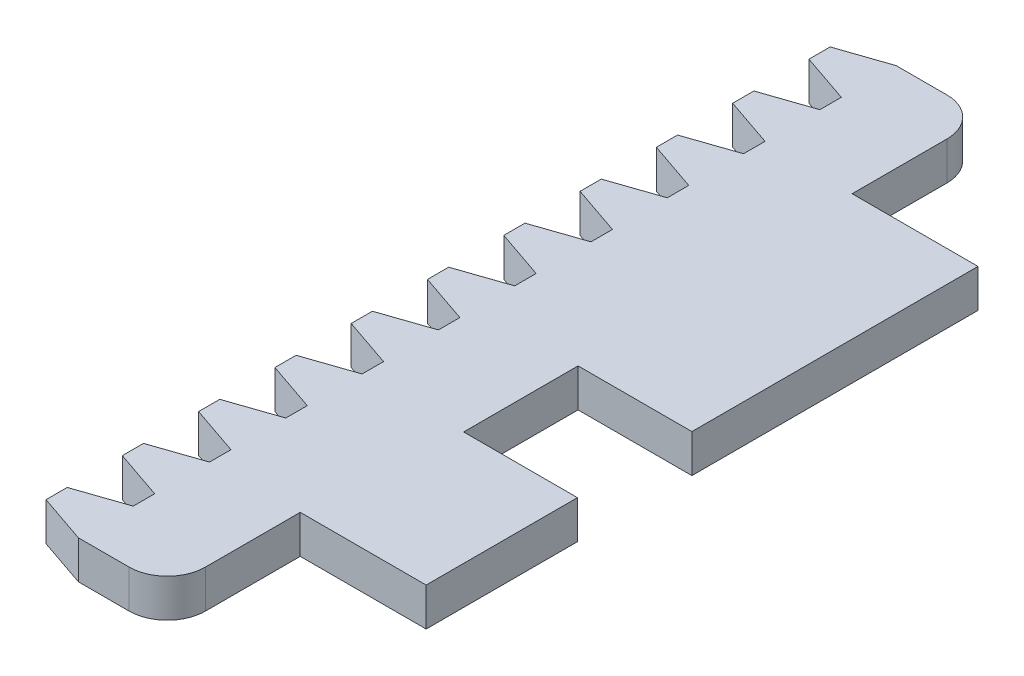
SolidWorks part; units mm, degrees
ref_plane "Front Plane" through (0, 0, 0) normal (0, 0, 1) x (1, 0, 0)
ref_plane "Top Plane" through (0, 0, 0) normal (0, 1, 0) x (1, 0, 0)
ref_plane "Right Plane" through (0, 0, 0) normal (1, 0, 0) x (0, 0, -1)
sketch "Sketch1" plane through (0, 0, 0) normal (0, 1, 0) x (1, 0, 0)
  line L4 (37.95, 21.7) -> (28.05, 21.7) construction
  line L5 (28.05, 29.157) -> (28.05, 21.7) construction
  line L6 (21.0585, 32.157) -> (25.05, 32.157) construction
  line L7 (21.0585, 32.157) -> (17.1887, 30.8335) construction
  line L8 (17.1887, 30.8335) -> (17.1887, 29.1665) construction
  line L13 (17.1887, 29.1665) -> (21.0585, 27.843) construction
  line L14 (21.0585, 26.157) -> (21.0585, 27.843) construction
  line L15 (21.0585, 26.157) -> (17.1887, 24.8335) construction
  line L16 (17.1887, 24.8335) -> (17.1887, 23.1665) construction
  line L17 (17.1887, 23.1665) -> (21.0585, 21.843) construction
  line L18 (21.0585, 20.157) -> (21.0585, 21.843) construction
  line L19 (21.0585, 20.157) -> (17.1887, 18.8335) construction
  line L20 (17.1887, 18.8335) -> (17.1887, 17.1665) construction
  line L21 (17.1887, 17.1665) -> (21.0585, 15.843) construction
  line L22 (21.0585, 14.157) -> (21.0585, 15.843) construction
  line L23 (21.0585, 14.157) -> (17.1887, 12.8335) construction
  line L24 (17.1887, 12.8335) -> (17.1887, 11.1665) construction
  line L25 (17.1887, 11.1665) -> (21.0585, 9.843) construction
  line L26 (21.0585, 8.157) -> (21.0585, 9.843) construction
  line L27 (21.0585, 8.157) -> (17.1887, 6.8335) construction
  line L28 (17.1887, 6.8335) -> (17.1887, 5.1665) construction
  line L29 (17.1887, 5.1665) -> (21.0585, 3.843) construction
  line L30 (21.0585, 2.157) -> (21.0585, 3.843) construction
  line L31 (21.0585, 2.157) -> (17.1887, 0.8335) construction
  line L32 (17.1887, 0.8335) -> (17.1887, -0.8335) construction
  line L33 (17.1887, -0.8335) -> (21.0585, -2.157) construction
  line L34 (21.0585, -3.843) -> (21.0585, -2.157) construction
  line L35 (21.0585, -3.843) -> (17.1887, -5.1665) construction
  line L36 (17.1887, -5.1665) -> (17.1887, -6.8335) construction
  line L37 (17.1887, -6.8335) -> (21.0585, -8.157) construction
  line L38 (21.0585, -9.843) -> (21.0585, -8.157) construction
  line L39 (21.0585, -9.843) -> (17.1887, -11.1665) construction
  line L40 (17.1887, -11.1665) -> (17.1887, -12.8335) construction
  line L41 (17.1887, -12.8335) -> (21.0585, -14.157) construction
  line L42 (21.0585, -15.843) -> (21.0585, -14.157) construction
  line L43 (21.0585, -15.843) -> (17.1887, -17.1665) construction
  line L44 (17.1887, -17.1665) -> (17.1887, -18.8335) construction
  line L45 (17.1887, -18.8335) -> (21.0585, -20.157) construction
  line L46 (21.0585, -21.843) -> (21.0585, -20.157) construction
  line L47 (21.0585, -21.843) -> (17.1887, -23.1665) construction
  line L48 (17.1887, -23.1665) -> (17.1887, -24.8335) construction
  line L49 (17.1887, -24.8335) -> (21.0585, -26.157) construction
  line L55 (21.0585, -27.843) -> (21.0585, -26.157) construction
  line L56 (21.0585, -27.843) -> (17.1887, -29.1665) construction
  line L57 (17.1887, -29.1665) -> (17.1887, -30.8335) construction
  line L99 (17.1887, -30.8335) -> (21.0585, -32.157) construction
  line L100 (25.05, -32.157) -> (21.0585, -32.157) construction
  line L105 (28.05, -21.7) -> (28.05, -29.157) construction
  line L107 (37.95, -21.7) -> (28.05, -21.7) construction
  line L108 (37.95, -9.8) -> (37.95, -21.7) construction
  line L109 (29, -9.8) -> (37.95, -9.8) construction
  line L110 (29, -0.8) -> (29, -9.8) construction
  line L111 (37.95, -0.8) -> (29, -0.8) construction
  line L112 (37.95, 21.7) -> (37.95, -0.8) construction
  line L113 (37.95, 21.7) -> (28.05, 21.7)
  line L114 (28.05, 29.157) -> (28.05, 21.7)
  line L115 (21.0585, 32.157) -> (25.05, 32.157)
  line L116 (21.0585, 32.157) -> (17.1887, 30.8335)
  line L117 (17.1887, 30.8335) -> (17.1887, 29.1665)
  line L118 (17.1887, 29.1665) -> (21.0585, 27.843)
  line L119 (21.0585, 26.157) -> (21.0585, 27.843)
  line L120 (21.0585, 26.157) -> (17.1887, 24.8335)
  line L121 (17.1887, 24.8335) -> (17.1887, 23.1665)
  line L122 (17.1887, 23.1665) -> (21.0585, 21.843)
  line L123 (21.0585, 20.157) -> (21.0585, 21.843)
  line L124 (21.0585, 20.157) -> (17.1887, 18.8335)
  line L125 (17.1887, 18.8335) -> (17.1887, 17.1665)
  line L126 (17.1887, 17.1665) -> (21.0585, 15.843)
  line L127 (21.0585, 14.157) -> (21.0585, 15.843)
  line L128 (21.0585, 14.157) -> (17.1887, 12.8335)
  line L129 (17.1887, 12.8335) -> (17.1887, 11.1665)
  line L130 (17.1887, 11.1665) -> (21.0585, 9.843)
  line L131 (21.0585, 8.157) -> (21.0585, 9.843)
  line L132 (21.0585, 8.157) -> (17.1887, 6.8335)
  line L133 (17.1887, 6.8335) -> (17.1887, 5.1665)
  line L134 (17.1887, 5.1665) -> (21.0585, 3.843)
  line L135 (21.0585, 2.157) -> (21.0585, 3.843)
  line L136 (21.0585, 2.157) -> (17.1887, 0.8335)
  line L137 (17.1887, 0.8335) -> (17.1887, -0.8335)
  line L138 (17.1887, -0.8335) -> (21.0585, -2.157)
  line L139 (21.0585, -3.843) -> (21.0585, -2.157)
  line L140 (21.0585, -3.843) -> (17.1887, -5.1665)
  line L141 (17.1887, -5.1665) -> (17.1887, -6.8335)
  line L142 (17.1887, -6.8335) -> (21.0585, -8.157)
  line L143 (21.0585, -9.843) -> (21.0585, -8.157)
  line L144 (21.0585, -9.843) -> (17.1887, -11.1665)
  line L145 (17.1887, -11.1665) -> (17.1887, -12.8335)
  line L146 (17.1887, -12.8335) -> (21.0585, -14.157)
  line L147 (21.0585, -15.843) -> (21.0585, -14.157)
  line L148 (21.0585, -15.843) -> (17.1887, -17.1665)
  line L149 (17.1887, -17.1665) -> (17.1887, -18.8335)
  line L150 (17.1887, -18.8335) -> (21.0585, -20.157)
  line L151 (21.0585, -21.843) -> (21.0585, -20.157)
  line L152 (21.0585, -21.843) -> (17.1887, -23.1665)
  line L153 (17.1887, -23.1665) -> (17.1887, -24.8335)
  line L154 (17.1887, -24.8335) -> (21.0585, -26.157)
  line L155 (21.0585, -27.843) -> (21.0585, -26.157)
  line L156 (21.0585, -27.843) -> (17.1887, -29.1665)
  line L157 (17.1887, -29.1665) -> (17.1887, -30.8335)
  line L160 (17.1887, -30.8335) -> (21.0585, -32.157)
  line L161 (25.05, -32.157) -> (21.0585, -32.157)
  line L162 (28.05, -21.7) -> (28.05, -29.157)
  line L163 (37.95, -21.7) -> (28.05, -21.7)
  line L164 (37.95, -9.8) -> (37.95, -21.7)
  line L165 (29, -9.8) -> (37.95, -9.8)
  line L166 (29, -0.8) -> (29, -9.8)
  line L167 (37.95, -0.8) -> (29, -0.8)
  line L168 (37.95, 21.7) -> (37.95, -0.8)
  line L169 (37.95, 28.7) -> (33.35, 28.7) construction
  line L170 (15.05, 32.157) -> (26.5, 32.157) construction
  line L171 (15.05, 32.157) -> (15.05, -32.157) construction
  line L172 (15.05, -32.157) -> (26.5, -32.157) construction
  line L173 (19.65, 32.157) -> (19.65, -32.157) construction
  line L174 (37.95, 28.7) -> (33.35, 28.7) construction
  line L175 (37.95, 28.7) -> (37.95, -28.7) construction
  line L176 (37.95, -28.7) -> (33.35, -28.7) construction
  line L177 (33.35, 28.7) -> (33.35, -28.7) construction
  line L178 (21.0585, 32.157) -> (15.05, 32.157) construction
  line L179 (15.05, -32.157) -> (21.0585, -32.157) construction
  line L180 (15.05, 32.157) -> (15.05, -32.157) construction
  line L181 (19.65, -32.157) -> (19.65, 32.157) construction
  line L182 (37.95, -28.7) -> (33.35, -28.7) construction
  line L183 (33.35, -28.7) -> (33.35, 28.7) construction
  line L184 (37.95, 28.7) -> (37.95, -28.7) construction
  line L185 (37.95, 0) -> (15.05, 0) construction
  line L186 (15.05, 0) -> (37.95, 0) construction
  line L187 (26.5, 32.157) -> (26.5, -32.157) construction
  line L188 (26.5, 32.157) -> (26.5, -32.157) construction
  line L189 (19.65, 21.7) -> (37.95, 21.7) construction
  line L190 (19.65, -21.7) -> (37.95, -21.7) construction
  line L191 (37.95, 21.7) -> (19.65, 21.7) construction
  line L192 (37.95, -3.8) -> (32, -3.8) construction
  line L193 (32, -3.8) -> (32, -6.8) construction
  line L194 (32, -6.8) -> (37.95, -6.8) construction
  line L195 (29, -5.3) -> (37.95, -5.3) construction
  line L196 (34.95, -0.8) -> (34.95, 18.7) construction
  line L197 (34.95, -9.8) -> (34.95, -18.7) construction
  line L198 (34.95, 18.7) -> (19.65, 18.7) construction
  line L199 (19.65, -18.7) -> (34.95, -18.7) construction
  line L200 (34.95, 18.7) -> (34.95, 21.7) construction
  line L201 (34.95, 18.7) -> (37.95, 18.7) construction
  line L202 (34.95, -18.7) -> (37.95, -18.7) construction
  line L203 (34.95, -18.7) -> (34.95, -21.7) construction
  line L204 (37.15, 28.7) -> (37.15, -28.7) construction
  line L205 (34.15, 28.7) -> (34.15, -28.7) construction
  line L206 (18.85, 32.157) -> (18.85, -32.157) construction
  line L207 (15.85, 32.157) -> (15.85, -32.157) construction
  line L208 (37.15, 28.7) -> (37.15, -0.8) construction
  line L209 (34.15, 28.7) -> (34.15, -0.8) construction
  line L210 (18.85, 32.157) -> (18.85, -32.157) construction
  line L211 (15.85, 32.157) -> (15.85, -32.157) construction
  line L212 (37.15, -9.8) -> (37.15, -28.7) construction
  line L213 (34.15, -9.8) -> (34.15, -28.7) construction
  arc A2 (28.05, 29.157) -> (25.05, 32.157) centre (25.05, 29.157) ccw construction
  arc A3 (25.05, -32.157) -> (28.05, -29.157) centre (25.05, -29.157) ccw construction
  arc A4 (28.05, 29.157) -> (25.05, 32.157) centre (25.05, 29.157) ccw
  arc A5 (25.05, -32.157) -> (28.05, -29.157) centre (25.05, -29.157) ccw
sketch "Sketch2" plane through (0, 0, 0) normal (0, 0, 1) x (1, 0, 0)
  line L1 (37.95, -3) -> (15.05, -3)
  line L2 (37.95, -3) -> (37.95, 0)
  line L3 (37.95, 0) -> (15.05, 0)
  line L4 (15.05, -3) -> (15.05, 0)
  line L5 (21, -3) -> (-21, -3) construction
extrude "Boss-Extrude1" add sketch "Sketch1" against normal up to vertex (3 mm away) up to point (15.05, -3, 0)
ref_plane "gear" through (0, 0, 3.8) normal (0, 0, 1) x (1, 0, 0)
ref_plane "front" through (0, 0, 21.7) normal (0, 0, 1) x (1, 0, 0)
ref_plane "back" through (0, 0, -21.7) normal (0, 0, 1) x (1, 0, 0)
ref_plane "top" through (37.15, 0, 0) normal (1, 0, 0) x (0, 0, -1)
ref_plane "bottom" through (15.85, 0, 0) normal (1, 0, 0) x (0, 0, -1)
